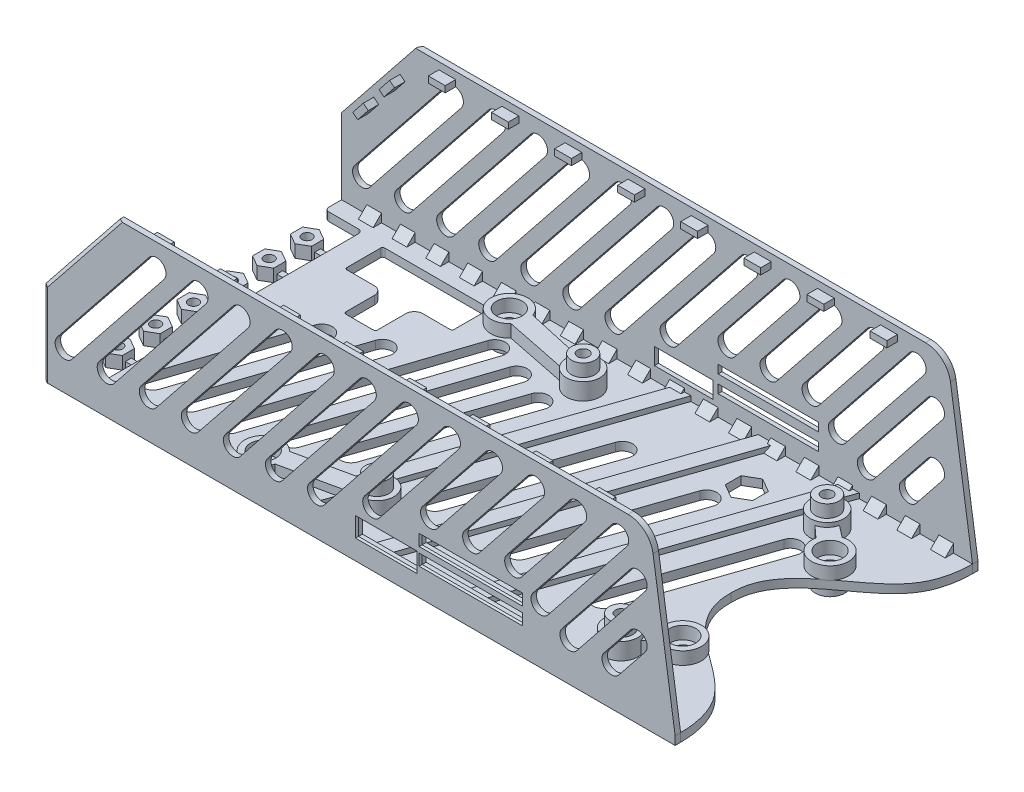
SolidWorks part; units mm, degrees
material "PPS"
ref_plane "前视基准面" through (0, 0, 0) normal (0, 0, 1) x (1, 0, 0)
ref_plane "上视基准面" through (0, 0, 0) normal (0, 1, 0) x (1, 0, 0)
ref_plane "右视基准面" through (0, 0, 0) normal (1, 0, 0) x (0, 0, -1)
sketch "草图1" plane through (0, 0, 0) normal (0, 1, 0) x (1, 0, 0)
  line L1 (-38.5883, 74.1339) -> (111.4117, 74.1339)
  line L2 (-38.5883, 74.1339) -> (-38.5883, 2.1339)
  line L3 (-38.5883, 2.1339) -> (111.4117, 2.1339)
  line L4 (111.4117, 74.1339) -> (111.4117, 2.1339)
  dimension "D1" = 72
  dimension "D2" = 150
extrude "底板" add sketch "草图1" against normal blind 2 contours L2 L1 L4 L3
sketch "草图2" plane through (0, 0, 0) normal (0, 1, 0) x (1, 0, 0)
  circle A3 centre (28.7548, 13.929) radius 4
  circle A4 centre (86.7548, 13.929) radius 4
  circle A5 centre (86.7548, 62.929) radius 4
  circle A6 centre (28.7548, 62.929) radius 4
  dimension "D1" = 2
  dimension "D2" = 2
extrude "板卡固定柱" add sketch "草图2" along normal blind 7
sketch "螺母孔" plane through (0, -2, 0) normal (0, -1, 0) x (1, 0, 0)
  line L0 (88.256, -11.329) -> (85.2537, -11.329)
  line L1 (30.256, -11.329) -> (27.2537, -11.329)
  line L2 (27.2537, -11.329) -> (25.7526, -13.929)
  line L3 (25.7526, -13.929) -> (27.2537, -16.529)
  line L4 (27.2537, -16.529) -> (30.256, -16.529)
  line L5 (30.256, -16.529) -> (31.7571, -13.929)
  line L6 (31.7571, -13.929) -> (30.256, -11.329)
  line L7 (85.2537, -11.329) -> (83.7526, -13.929)
  line L8 (83.7526, -13.929) -> (85.2537, -16.529)
  line L9 (85.2537, -16.529) -> (88.256, -16.529)
  line L10 (88.256, -16.529) -> (89.7571, -13.929)
  line L11 (89.7571, -13.929) -> (88.256, -11.329)
  line L12 (88.256, -60.329) -> (85.2537, -60.329)
  line L13 (85.2537, -60.329) -> (83.7526, -62.929)
  line L14 (83.7526, -62.929) -> (85.2537, -65.529)
  line L15 (85.2537, -65.529) -> (88.256, -65.529)
  line L16 (88.256, -65.529) -> (89.7571, -62.929)
  line L17 (89.7571, -62.929) -> (88.256, -60.329)
  line L18 (30.256, -60.329) -> (27.2537, -60.329)
  line L19 (27.2537, -60.329) -> (25.7526, -62.929)
  line L20 (25.7526, -62.929) -> (27.2537, -65.529)
  line L21 (27.2537, -65.529) -> (30.256, -65.529)
  line L22 (30.256, -65.529) -> (31.7571, -62.929)
  line L23 (31.7571, -62.929) -> (30.256, -60.329)
  circle A0 centre (28.7548, -13.929) radius 2.6 construction
  circle A1 centre (28.7548, -13.929) radius 4 construction
  circle A2 centre (86.7548, -13.929) radius 2.6 construction
  circle A3 centre (86.7548, -62.929) radius 2.6 construction
  circle A4 centre (28.7548, -62.929) radius 2.6 construction
  dimension "D1" = 2
  dimension "D2" = 2
extrude "m2.5螺母孔槽" cut sketch "螺母孔" against normal blind 5
sketch "草图4" plane through (0, 3, 0) normal (0, -1, 0) x (1, 0, 0)
  circle A0 centre (28.7548, -13.929) radius 1.35
  circle A1 centre (28.7548, -13.929) radius 4 construction
  circle A2 centre (86.7548, -13.929) radius 1.35
  circle A3 centre (86.7548, -62.929) radius 1.35
  circle A4 centre (28.7548, -62.929) radius 1.35
  dimension "D1" = 2
  dimension "D2" = 2
extrude "m2.5通孔" cut sketch "草图4" against normal up to next
sketch "草图6" plane through (0, 7, 0) normal (0, 1, 0) x (1, 0, 0)
  circle A0 centre (28.7548, 13.929) radius 4
  circle A1 centre (28.7548, 13.929) radius 2.7944
  circle A2 centre (86.7548, 13.929) radius 4
  circle A3 centre (86.7548, 13.929) radius 2.7944
  circle A4 centre (86.7548, 62.929) radius 4
  circle A5 centre (86.7548, 62.929) radius 2.7944
  circle A6 centre (28.7548, 62.929) radius 4
  circle A7 centre (28.7548, 62.929) radius 2.7944
  dimension "D1" = 2
  dimension "D2" = 2
extrude "切除-拉伸3" cut sketch "草图6" against normal blind 3
sketch "侧边" plane through (0, 0, -74.1339) normal (0, 0, -1) x (-1, 0, 0)
  line L0 (-74.7943, 6.8381) -> (-50.9153, 6.8381)
  line L1 (-111.4117, 0) -> (38.5883, 0)
  line L6 (-74.7943, 10.8959) -> (-50.9153, 10.8959)
  line L8 (-74.7943, 10.8959) -> (-74.7943, 8.8959)
  line L9 (-74.7943, 4.8381) -> (-50.9153, 4.8381)
  line L10 (-50.9153, 4.8381) -> (-50.9153, 6.8381)
  line L11 (-74.7943, 8.8959) -> (-50.9153, 8.8959)
  line L12 (-74.7943, 6.8381) -> (-74.7943, 4.8381)
  line L13 (-50.9153, 8.8959) -> (-50.9153, 10.8959)
  line L16 (-49.6686, 3.0554) -> (-35.7948, 3.0554)
  line L17 (-35.7948, 3.0554) -> (-35.7948, 7)
  line L18 (-35.7948, 7) -> (-49.6686, 7)
  line L19 (-49.6686, 7) -> (-49.6686, 3.0554)
  line L21 (38.5883, -2) -> (38.5883, 0) construction
  line L22 (20.9589, 40) -> (-100.2254, 40)
  line L23 (-106.1585, 34.8932) -> (-111.4117, 0)
  line L25 (38.5883, 0) -> (38.5883, 17.9447)
  line L26 (38.5883, 17.9447) -> (20.9589, 40)
  line L27 (33.7328, 7.228) -> (11.8797, 34.5674) construction
  line L28 (31.9753, 5.8231) -> (10.1222, 33.1625)
  line L29 (35.4903, 8.6328) -> (13.6373, 35.9722)
  line L30 (23.7328, 7.228) -> (1.8797, 34.5674) construction
  line L31 (21.9753, 5.8231) -> (0.1222, 33.1625)
  line L32 (25.4903, 8.6328) -> (3.6373, 35.9722)
  line L33 (13.7328, 7.228) -> (-8.1203, 34.5674) construction
  line L34 (11.9753, 5.8231) -> (-9.8778, 33.1625)
  line L35 (15.4903, 8.6328) -> (-6.3627, 35.9722)
  line L36 (3.7328, 7.228) -> (-18.1203, 34.5674) construction
  line L37 (1.9753, 5.8231) -> (-19.8778, 33.1625)
  line L38 (5.4903, 8.6328) -> (-16.3627, 35.9722)
  line L39 (-6.2672, 7.228) -> (-28.1203, 34.5674) construction
  line L40 (-8.0247, 5.8231) -> (-29.8778, 33.1625)
  line L41 (-4.5097, 8.6328) -> (-26.3627, 35.9722)
  line L42 (-16.2672, 7.228) -> (-38.1203, 34.5674) construction
  line L43 (-18.0247, 5.8231) -> (-39.8778, 33.1625)
  line L44 (-14.5097, 8.6328) -> (-36.3627, 35.9722)
  line L45 (-26.2672, 7.228) -> (-48.1203, 34.5674) construction
  line L46 (-28.0247, 5.8231) -> (-49.8778, 33.1625)
  line L47 (-24.5097, 8.6328) -> (-46.3627, 35.9722)
  line L48 (-39.3891, 11.1336) -> (-58.1203, 34.5674) construction
  line L49 (-41.1466, 9.7287) -> (-59.8778, 33.1625)
  line L50 (-37.6315, 12.5384) -> (-56.3627, 35.9722)
  line L51 (-53.1353, 15.8203) -> (-68.1203, 34.5674) construction
  line L52 (-54.8928, 14.4155) -> (-69.8778, 33.1625)
  line L53 (-51.3778, 17.2252) -> (-66.3627, 35.9722)
  line L54 (-63.1353, 15.8203) -> (-78.1203, 34.5674) construction
  line L55 (-64.8928, 14.4155) -> (-79.8778, 33.1625)
  line L56 (-61.3778, 17.2252) -> (-76.3627, 35.9722)
  line L57 (-73.1353, 15.8203) -> (-88.1203, 34.5674) construction
  line L58 (-74.8928, 14.4155) -> (-89.8778, 33.1625)
  line L59 (-71.3778, 17.2252) -> (-86.3627, 35.9722)
  line L60 (-79.3891, 11.1336) -> (-98.1203, 34.5674) construction
  line L61 (-81.1466, 9.7287) -> (-99.8778, 33.1625)
  line L62 (-77.6315, 12.5384) -> (-96.3627, 35.9722)
  line L63 (-86.2672, 7.228) -> (-102.5009, 27.5372) construction
  line L64 (-88.0247, 5.8231) -> (-104.2584, 26.1324)
  line L65 (-84.5097, 8.6328) -> (-100.7434, 28.9421)
  line L66 (-96.2672, 7.228) -> (-102.5109, 15.0392) construction
  line L67 (-98.0247, 5.8231) -> (-104.2685, 13.6344)
  line L68 (-94.5097, 8.6328) -> (-100.7534, 16.4441)
  arc A0 (-100.2254, 40) -> (-106.1585, 34.8932) centre (-100.2254, 34) ccw
  arc A1 (31.9753, 5.8231) -> (35.4903, 8.6328) centre (33.7328, 7.228) ccw
  arc A2 (13.6373, 35.9722) -> (10.1222, 33.1625) centre (11.8797, 34.5674) ccw
  arc A3 (21.9753, 5.8231) -> (25.4903, 8.6328) centre (23.7328, 7.228) ccw
  arc A4 (3.6373, 35.9722) -> (0.1222, 33.1625) centre (1.8797, 34.5674) ccw
  arc A5 (11.9753, 5.8231) -> (15.4903, 8.6328) centre (13.7328, 7.228) ccw
  arc A6 (-6.3627, 35.9722) -> (-9.8778, 33.1625) centre (-8.1203, 34.5674) ccw
  arc A7 (1.9753, 5.8231) -> (5.4903, 8.6328) centre (3.7328, 7.228) ccw
  arc A8 (-16.3627, 35.9722) -> (-19.8778, 33.1625) centre (-18.1203, 34.5674) ccw
  arc A9 (-8.0247, 5.8231) -> (-4.5097, 8.6328) centre (-6.2672, 7.228) ccw
  arc A10 (-26.3627, 35.9722) -> (-29.8778, 33.1625) centre (-28.1203, 34.5674) ccw
  arc A11 (-18.0247, 5.8231) -> (-14.5097, 8.6328) centre (-16.2672, 7.228) ccw
  arc A12 (-36.3627, 35.9722) -> (-39.8778, 33.1625) centre (-38.1203, 34.5674) ccw
  arc A13 (-28.0247, 5.8231) -> (-24.5097, 8.6328) centre (-26.2672, 7.228) ccw
  arc A14 (-46.3627, 35.9722) -> (-49.8778, 33.1625) centre (-48.1203, 34.5674) ccw
  arc A15 (-41.1466, 9.7287) -> (-37.6315, 12.5384) centre (-39.3891, 11.1336) ccw
  arc A16 (-56.3627, 35.9722) -> (-59.8778, 33.1625) centre (-58.1203, 34.5674) ccw
  arc A17 (-54.8928, 14.4155) -> (-51.3778, 17.2252) centre (-53.1353, 15.8203) ccw
  arc A18 (-66.3627, 35.9722) -> (-69.8778, 33.1625) centre (-68.1203, 34.5674) ccw
  arc A19 (-64.8928, 14.4155) -> (-61.3778, 17.2252) centre (-63.1353, 15.8203) ccw
  arc A20 (-76.3627, 35.9722) -> (-79.8778, 33.1625) centre (-78.1203, 34.5674) ccw
  arc A21 (-74.8928, 14.4155) -> (-71.3778, 17.2252) centre (-73.1353, 15.8203) ccw
  arc A22 (-86.3627, 35.9722) -> (-89.8778, 33.1625) centre (-88.1203, 34.5674) ccw
  arc A23 (-81.1466, 9.7287) -> (-77.6315, 12.5384) centre (-79.3891, 11.1336) ccw
  arc A24 (-96.3627, 35.9722) -> (-99.8778, 33.1625) centre (-98.1203, 34.5674) ccw
  arc A25 (-88.0247, 5.8231) -> (-84.5097, 8.6328) centre (-86.2672, 7.228) ccw
  arc A26 (-100.7434, 28.9421) -> (-104.2584, 26.1324) centre (-102.5009, 27.5372) ccw
  arc A27 (-98.0247, 5.8231) -> (-94.5097, 8.6328) centre (-96.2672, 7.228) ccw
  arc A28 (-100.7534, 16.4441) -> (-104.2685, 13.6344) centre (-102.5109, 15.0392) ccw
  point P2 (22.8063, 20.8977)
  point P26 (0, 0)
  point P27 (0, 0)
  point P30 (0, 0)
  point P31 (12.8063, 20.8977)
  point P38 (2.8063, 20.8977)
  point P40 (0, 0)
  point P48 (-7.1937, 20.8977)
  point P55 (-17.1937, 20.8977)
  point P62 (-27.1937, 20.8977)
  point P69 (-37.1937, 20.8977)
  point P76 (-48.7547, 22.8505)
  point P83 (-60.6278, 25.1939)
  point P90 (-70.6278, 25.1939)
  point P97 (-80.6278, 25.1939)
  point P104 (-88.7547, 22.8505)
  point P111 (-94.384, 17.3826)
  point P118 (-99.3891, 11.1336)
  point P125 (0, 0)
  point P126 (0, 0)
  point P127 (0, 0)
  point P128 (0, 0)
  point P129 (0, 0)
  point P130 (0, 0)
  point P131 (0, 0)
  point P132 (0, 0)
  point P133 (0, 0)
  point P134 (0, 0)
  point P135 (0, 0)
  point P136 (0, 0)
  point P137 (0, 0)
  point P138 (0, 0)
  dimension "D1" = 6
  dimension "D2" = 40
extrude "侧边凸台" add sketch "侧边" against normal blind 1.3
sketch "草图14" plane through (0, 0, -72.8339) normal (0, 0, 1) x (1, 0, 0)
  line L0 (-30.9262, 24.9677) -> (-33.4237, 21.8432)
  line L1 (-33.4237, 21.8432) -> (-32.2521, 20.9067)
  line L2 (-24.6825, 32.779) -> (-27.18, 29.6545)
  line L3 (-27.18, 29.6545) -> (-26.0083, 28.7179)
  line L4 (-26.0083, 28.7179) -> (-23.5108, 31.8424)
  line L5 (-23.5108, 31.8424) -> (-24.6825, 32.779)
  line L6 (-32.2521, 20.9067) -> (-29.7546, 24.0312)
  line L7 (-29.7546, 24.0312) -> (-30.9262, 24.9677)
  line L9 (-15.4544, 38.32) -> (-11.4544, 38.32)
  line L10 (-11.4544, 38.32) -> (-11.4544, 36.82)
  line L11 (-11.4544, 36.82) -> (-15.4544, 36.82)
  line L12 (-15.4544, 36.82) -> (-15.4544, 38.32)
  line L13 (-20.9589, 40) -> (100.2254, 40) construction
  line L14 (-0.4544, 38.32) -> (3.5456, 38.32)
  line L15 (3.5456, 38.32) -> (3.5456, 36.82)
  line L16 (3.5456, 36.82) -> (-0.4544, 36.82)
  line L17 (-0.4544, 36.82) -> (-0.4544, 38.32)
  line L18 (14.5456, 38.32) -> (18.5456, 38.32)
  line L19 (18.5456, 38.32) -> (18.5456, 36.82)
  line L20 (18.5456, 36.82) -> (14.5456, 36.82)
  line L21 (14.5456, 36.82) -> (14.5456, 38.32)
  line L22 (29.5456, 38.32) -> (33.5456, 38.32)
  line L23 (33.5456, 38.32) -> (33.5456, 36.82)
  line L24 (33.5456, 36.82) -> (29.5456, 36.82)
  line L25 (29.5456, 36.82) -> (29.5456, 38.32)
  line L26 (44.5456, 38.32) -> (48.5456, 38.32)
  line L27 (48.5456, 38.32) -> (48.5456, 36.82)
  line L28 (48.5456, 36.82) -> (44.5456, 36.82)
  line L29 (44.5456, 36.82) -> (44.5456, 38.32)
  line L30 (59.5456, 38.32) -> (63.5456, 38.32)
  line L31 (63.5456, 38.32) -> (63.5456, 36.82)
  line L32 (63.5456, 36.82) -> (59.5456, 36.82)
  line L33 (59.5456, 36.82) -> (59.5456, 38.32)
  line L34 (74.5456, 38.32) -> (78.5456, 38.32)
  line L35 (78.5456, 38.32) -> (78.5456, 36.82)
  line L36 (78.5456, 36.82) -> (74.5456, 36.82)
  line L37 (74.5456, 36.82) -> (74.5456, 38.32)
  line L38 (89.5456, 38.32) -> (93.5456, 38.32)
  line L39 (93.5456, 38.32) -> (93.5456, 36.82)
  line L40 (93.5456, 36.82) -> (89.5456, 36.82)
  line L41 (89.5456, 36.82) -> (89.5456, 38.32)
  dimension "D1" = 2
  dimension "D2" = 1.68
  dimension "D3" = 1.5
  dimension "D4" = 4
  dimension "D5" = 8
extrude "顶盖支架" add sketch "草图14" along normal blind 2.5
sketch "草图15" plane through (0, -2, 0) normal (0, -1, 0) x (1, 0, 0)
  line L0 (-38.5883, -38.1339) -> (111.4117, -38.1339)
  line L1 (-38.5883, -74.1339) -> (-38.5883, -2.1339) construction
  line L2 (111.4117, -74.1339) -> (111.4117, -2.1339) construction
ref_plane "基准面7" through (0, 0, -38.1339) normal (0, 0, -1) x (-1, 0, 0)
mirror "镜向1" about plane through (0, 0, -38.1339) normal (0, 0, -1) of "侧边凸台", "顶盖支架"
sketch "草图17" plane through (0, -2, 0) normal (0, -1, 0) x (1, 0, 0)
  line L0 (-7.5175, -59.0417) -> (1.4825, -59.0417)
  line L1 (1.4825, -59.0417) -> (1.4825, -68.0417)
  line L6 (1.4825, -68.0417) -> (-24.0175, -68.0417)
  line L7 (-24.0175, -68.0417) -> (-24.0175, -59.0417)
  line L8 (-24.0175, -59.0417) -> (-15.0175, -59.0417)
  line L9 (6.7325, -8.8917) -> (6.7325, -67.3917)
  line L10 (6.7325, -67.3917) -> (6.7325, -38.1417)
  line L11 (-7.5175, -49.7917) -> (-15.0175, -49.7917)
  line L12 (-7.5175, -59.0417) -> (-7.5175, -49.7917)
  line L14 (-15.0175, -49.7917) -> (-15.0175, -59.0417)
  line L15 (6.7325, -38.1417) -> (17.9206, -38.1417)
  circle A6 centre (6.7325, -67.3917) radius 1.55
  circle A7 centre (94.7325, -55.6417) radius 1.55
  circle A8 centre (6.7325, -67.3917) radius 1.55
  circle A9 centre (94.7325, -20.6417) radius 1.55
  circle A10 centre (6.7325, -8.8917) radius 1.55
  dimension "D1" = 9
  dimension "D2" = 9
  dimension "D3" = 9
  dimension "D4" = 58.5
extrude "链接孔" cut sketch "草图17" against normal blind 7 and the other way blind 13 contours A6 | L11 L14 L12 | A7 | A9 | A10 region at (-11.2675, -2, -61.4236) region at (7.7975, -2, -66.3267)
sketch "草图27" plane through (0, -2, 0) normal (0, -1, 0) x (1, 0, 0)
  circle A0 centre (94.7325, -55.6417) radius 3.5
  circle A1 centre (94.7325, -20.6417) radius 3.5
  circle A2 centre (6.7325, -67.3917) radius 3.5
  circle A3 centre (6.7325, -8.8917) radius 3.5
  dimension "D1" = 7
extrude "凸台-拉伸9" add sketch "草图27" along normal blind 2
sketch "草图18" plane through (0, 0, 0) normal (0, 1, 0) x (1, 0, 0)
  line L0 (-38.5883, 7.4339) -> (-38.5883, 68.8339)
  line L13 (-23.5883, 13.0192) -> (-13.5883, 43.1339) construction
  line L14 (23.1, 38.1339) -> (-23.1, 38.1339) construction
  line L15 (-25.9609, 13.8071) -> (-15.9609, 43.9218)
  line L22 (-21.2157, 12.2314) -> (-11.2157, 42.3461)
  line L23 (-38.5883, 7.4339) -> (-30.5883, 7.4339)
  line L24 (-29.5883, 8.4339) -> (-29.5883, 67.8339)
  line L25 (-30.5883, 68.8339) -> (-38.5883, 68.8339)
  line L26 (-38.5883, 38.1339) -> (111.4117, 38.1339) construction
  line L27 (-14.5883, 13.0192) -> (-3.2431, 47.1848) construction
  line L28 (-16.9609, 13.8071) -> (-5.6157, 47.9727)
  line L29 (-12.2157, 12.2314) -> (-0.8705, 46.3969)
  line L30 (-5.5883, 13.0192) -> (10.1689, 60.4714) construction
  line L31 (-7.9609, 13.8071) -> (7.7963, 61.2593)
  line L32 (-3.2157, 12.2314) -> (12.5415, 59.6836)
  line L33 (4.9874, 17.7644) -> (18.2234, 57.6243) construction
  line L34 (2.6148, 18.5523) -> (15.8508, 58.4121)
  line L35 (7.36, 16.9766) -> (20.596, 56.8364)
  line L36 (14.9242, 21.5786) -> (26.2679, 54.6893) construction
  line L37 (12.5591, 22.3889) -> (23.9029, 55.4996)
  line L38 (17.2892, 20.7683) -> (28.633, 53.879)
  line L39 (111.4117, 72.8339) -> (-38.5883, 72.8339) construction
  line L41 (111.4117, 72.8339) -> (111.4117, 3.4339)
  line L44 (34.9242, 21.5786) -> (46.2679, 54.6893) construction
  line L45 (32.5591, 22.3889) -> (43.9029, 55.4996)
  line L46 (37.2892, 20.7683) -> (48.633, 53.879)
  line L50 (54.9242, 21.5786) -> (66.2679, 54.6893) construction
  line L51 (52.5591, 22.3889) -> (63.9029, 55.4996)
  line L52 (57.2892, 20.7683) -> (68.633, 53.879)
  line L56 (74.9242, 21.5786) -> (86.2679, 54.6893) construction
  line L57 (72.5591, 22.3889) -> (83.9029, 55.4996)
  line L58 (77.2892, 20.7683) -> (88.633, 53.879)
  line L264 (44.9242, 21.5786) -> (56.2679, 54.6893) construction
  line L265 (42.5591, 22.3889) -> (53.9029, 55.4996)
  line L266 (47.2892, 20.7683) -> (58.633, 53.879)
  line L267 (64.9242, 21.5786) -> (76.2679, 54.6893) construction
  line L268 (62.5591, 22.3889) -> (73.9029, 55.4996)
  line L269 (67.2892, 20.7683) -> (78.633, 53.879)
  line L270 (24.9242, 21.5786) -> (36.2679, 54.6893) construction
  line L271 (22.5591, 22.3889) -> (33.9029, 55.4996)
  line L272 (27.2892, 20.7683) -> (38.633, 53.879)
  line L273 (44.9242, 21.5786) -> (56.2679, 54.6893) construction
  line L274 (42.5591, 22.3889) -> (53.9029, 55.4996)
  line L275 (47.2892, 20.7683) -> (58.633, 53.879)
  line L276 (64.9242, 21.5786) -> (76.2679, 54.6893) construction
  line L277 (62.5591, 22.3889) -> (73.9029, 55.4996)
  line L278 (67.2892, 20.7683) -> (78.633, 53.879)
  line L279 (24.9242, 21.5786) -> (36.2679, 54.6893) construction
  line L280 (22.5591, 22.3889) -> (33.9029, 55.4996)
  line L281 (27.2892, 20.7683) -> (38.633, 53.879)
  arc A2 (-25.9609, 13.8071) -> (-21.2157, 12.2314) centre (-23.5883, 13.0192) ccw
  arc A3 (-11.2157, 42.3461) -> (-15.9609, 43.9218) centre (-13.5883, 43.1339) ccw
  arc A4 (-16.9609, 13.8071) -> (-12.2157, 12.2314) centre (-14.5883, 13.0192) ccw
  arc A5 (-0.8705, 46.3969) -> (-5.6157, 47.9727) centre (-3.2431, 47.1848) ccw
  arc A6 (-7.9609, 13.8071) -> (-3.2157, 12.2314) centre (-5.5883, 13.0192) ccw
  arc A7 (12.5415, 59.6836) -> (7.7963, 61.2593) centre (10.1689, 60.4714) ccw
  arc A8 (2.6148, 18.5523) -> (7.36, 16.9766) centre (4.9874, 17.7644) ccw
  arc A9 (20.596, 56.8364) -> (15.8508, 58.4121) centre (18.2234, 57.6243) ccw
  arc A10 (12.5591, 22.3889) -> (17.2892, 20.7683) centre (14.9242, 21.5786) ccw
  arc A11 (28.633, 53.879) -> (23.9029, 55.4996) centre (26.2679, 54.6893) ccw
  arc A18 (-30.5883, 7.4339) -> (-29.5883, 8.4339) centre (-30.5883, 8.4339) ccw
  arc A19 (-29.5883, 67.8339) -> (-30.5883, 68.8339) centre (-30.5883, 67.8339) ccw
  arc A21 (32.5591, 22.3889) -> (37.2892, 20.7683) centre (34.9242, 21.5786) ccw
  arc A22 (48.633, 53.879) -> (43.9029, 55.4996) centre (46.2679, 54.6893) ccw
  arc A25 (52.5591, 22.3889) -> (57.2892, 20.7683) centre (54.9242, 21.5786) ccw
  arc A26 (68.633, 53.879) -> (63.9029, 55.4996) centre (66.2679, 54.6893) ccw
  arc A29 (72.5591, 22.3889) -> (77.2892, 20.7683) centre (74.9242, 21.5786) ccw
  arc A30 (88.633, 53.879) -> (83.9029, 55.4996) centre (86.2679, 54.6893) ccw
  arc A174 (42.5591, 22.3889) -> (47.2892, 20.7683) centre (44.9242, 21.5786) ccw
  arc A175 (58.633, 53.879) -> (53.9029, 55.4996) centre (56.2679, 54.6893) ccw
  arc A176 (62.5591, 22.3889) -> (67.2892, 20.7683) centre (64.9242, 21.5786) ccw
  arc A177 (78.633, 53.879) -> (73.9029, 55.4996) centre (76.2679, 54.6893) ccw
  arc A178 (22.5591, 22.3889) -> (27.2892, 20.7683) centre (24.9242, 21.5786) ccw
  arc A179 (38.633, 53.879) -> (33.9029, 55.4996) centre (36.2679, 54.6893) ccw
  spline S0 degree 3 poles (111.4117, 72.8339) (111.3592, 67.7048) (109.4998, 62.8559) (100.5415, 53.3454) (88.3796, 48.3908) (88.633, 38.1339) knots 0 0 0 0 0.239028 0.339028 1 1 1 1
  spline S1 degree 3 poles (111.4117, 3.4339) (111.3592, 8.5631) (109.4998, 13.412) (100.5415, 22.9225) (88.3796, 27.8771) (88.633, 38.1339) knots 0 0 0 0 0.239028 0.339028 1 1 1 1
  point P6 (50.596, 38.1339)
  point P20 (-18.5883, 28.0766)
  point P31 (-8.9157, 30.102)
  point P38 (2.2903, 36.7453)
  point P44 (40.596, 38.1339)
  point P47 (11.6054, 37.6944)
  point P54 (20.596, 38.1339)
  point P65 (30.596, 38.1339)
  point P68 (28.7548, 38.1339)
  point P72 (70.596, 38.1339)
  point P82 (-29.5883, 7.4339)
  point P87 (60.596, 38.1339)
  point P101 (80.596, 38.1339)
  point P109 (50.596, 38.1339)
  point P116 (70.596, 38.1339)
  point P123 (30.596, 38.1339)
  point P130 (50.596, 38.1339)
  point P137 (70.596, 38.1339)
  point P144 (30.596, 38.1339)
  point P151 (50.596, 38.1339)
  point P158 (70.596, 38.1339)
  point P165 (30.596, 38.1339)
  point P172 (50.596, 38.1339)
  point P179 (70.596, 38.1339)
  point P186 (30.596, 38.1339)
  point P193 (50.596, 38.1339)
  point P200 (70.596, 38.1339)
  point P207 (30.596, 38.1339)
  point P214 (50.596, 38.1339)
  point P221 (70.596, 38.1339)
  point P228 (30.596, 38.1339)
  point P235 (50.596, 38.1339)
  point P242 (70.596, 38.1339)
  point P249 (30.596, 38.1339)
  point P256 (50.596, 38.1339)
  point P263 (70.596, 38.1339)
  point P270 (30.596, 38.1339)
  point P277 (50.596, 38.1339)
  point P284 (70.596, 38.1339)
  point P291 (30.596, 38.1339)
  point P298 (50.596, 38.1339)
  point P305 (70.596, 38.1339)
  point P312 (30.596, 38.1339)
  point P319 (50.596, 38.1339)
  point P326 (70.596, 38.1339)
  point P333 (30.596, 38.1339)
  point P340 (50.596, 38.1339)
  point P347 (70.596, 38.1339)
  point P354 (30.596, 38.1339)
  point P361 (50.596, 38.1339)
  point P368 (70.596, 38.1339)
  point P375 (30.596, 38.1339)
  point P382 (50.596, 38.1339)
  point P389 (70.596, 38.1339)
  point P396 (30.596, 38.1339)
  point P403 (50.596, 38.1339)
  point P410 (70.596, 38.1339)
  point P417 (30.596, 38.1339)
  point P424 (50.596, 38.1339)
  point P431 (70.596, 38.1339)
  point P438 (30.596, 38.1339)
  point P445 (50.596, 38.1339)
  point P452 (70.596, 38.1339)
  point P459 (30.596, 38.1339)
  point P466 (50.596, 38.1339)
  point P473 (70.596, 38.1339)
  point P480 (30.596, 38.1339)
  point P487 (50.596, 38.1339)
  point P494 (70.596, 38.1339)
  point P501 (30.596, 38.1339)
  point P508 (50.596, 38.1339)
  point P515 (70.596, 38.1339)
  point P522 (30.596, 38.1339)
  point P529 (50.596, 38.1339)
  point P536 (70.596, 38.1339)
  point P543 (30.596, 38.1339)
  point P550 (50.596, 38.1339)
  point P557 (70.596, 38.1339)
  point P564 (30.596, 38.1339)
  point P571 (50.596, 38.1339)
  point P578 (70.596, 38.1339)
  point P585 (30.596, 38.1339)
  point P592 (50.596, 38.1339)
  point P599 (70.596, 38.1339)
  point P606 (30.596, 38.1339)
  dimension "D8" = 2.5
  dimension "D1" = 0
  dimension "D2" = 7
  dimension "D6" = 9
  dimension "D7" = 6
  dimension "D9" = 5
  dimension "D10" = 16
  dimension "D11" = 12.3625
extrude "切除-拉伸6" cut sketch "草图18" against normal up to next
fillet "圆角3" radius 1 2 edges at (-38.5883, -1, -7.4339) (-38.5883, -1, -68.8339)
sketch "草图21" plane through (0, 0, 0) normal (0, 1, 0) x (1, 0, 0)
  line L19 (25.2623, 61.392) -> (10.0302, 64.4787)
  line L21 (25.8951, 65.4552) -> (10.904, 68.7911)
  line L24 (25.2432, 15.1377) -> (9.9931, 11.8461)
  line L26 (26.1715, 10.8368) -> (10.9214, 7.5452)
  line L32 (90.4004, 19.8717) -> (87.7239, 17.6196)
  line L33 (93.2333, 16.505) -> (90.5117, 14.5967)
  line L36 (87.573, 59.202) -> (90.4353, 56.5873)
  line L38 (90.4814, 62.1089) -> (93.4028, 59.836)
  arc A12 (10.904, 68.7911) -> (10.0302, 64.4787) centre (6.7325, 67.3917) ccw
  circle A13 centre (6.7325, 67.3917) radius 3.05
  arc A14 (25.8951, 65.4552) -> (25.2623, 61.392) centre (28.7548, 62.929) ccw
  arc A15 (9.9931, 11.8461) -> (10.9214, 7.5452) centre (6.7325, 8.8917) ccw
  circle A16 centre (6.7325, 8.8917) radius 3.05
  arc A17 (25.2432, 15.1377) -> (26.1715, 10.8368) centre (28.9728, 13.692) ccw
  arc A18 (93.2333, 16.505) -> (90.4004, 19.8717) centre (94.7325, 20.6417) ccw
  circle A19 centre (94.7325, 20.6417) radius 3.05
  arc A20 (90.5117, 14.5967) -> (87.7239, 17.6196) centre (86.7548, 13.929) ccw
  arc A21 (90.4353, 56.5873) -> (93.4028, 59.836) centre (94.7325, 55.6417) ccw
  circle A22 centre (94.7325, 55.6417) radius 3.05
  arc A23 (87.573, 59.202) -> (90.4814, 62.1089) centre (86.7548, 62.929) ccw
  dimension "D1" = 6.1
  dimension "D2" = 4.4
extrude "板卡固定加强筋" add sketch "草图21" along normal blind 3
sketch "草图23" plane through (0, 0, 0) normal (0, 1, 0) x (1, 0, 0)
  line L0 (111.4117, 72.8339) -> (-38.5883, 72.8339) construction
  line L1 (-32.5883, 72.8339) -> (-29.0883, 72.8339)
  line L2 (-32.5883, 72.8339) -> (-32.5883, 70.8339)
  line L3 (-32.5883, 70.8339) -> (-29.0883, 70.8339)
  line L4 (-29.0883, 72.8339) -> (-29.0883, 70.8339)
  line L5 (-24.5883, 72.8339) -> (-24.5883, 70.8339)
  line L6 (-24.5883, 72.8339) -> (-21.0883, 72.8339)
  line L7 (-24.5883, 70.8339) -> (-21.0883, 70.8339)
  line L8 (-21.0883, 72.8339) -> (-21.0883, 70.8339)
  line L9 (-16.5883, 72.8339) -> (-16.5883, 70.8339)
  line L10 (-16.5883, 72.8339) -> (-13.0883, 72.8339)
  line L11 (-16.5883, 70.8339) -> (-13.0883, 70.8339)
  line L12 (-13.0883, 72.8339) -> (-13.0883, 70.8339)
  line L13 (-8.5883, 72.8339) -> (-8.5883, 70.8339)
  line L14 (-8.5883, 72.8339) -> (-5.0883, 72.8339)
  line L15 (-8.5883, 70.8339) -> (-5.0883, 70.8339)
  line L16 (-5.0883, 72.8339) -> (-5.0883, 70.8339)
  line L17 (-0.5883, 72.8339) -> (-0.5883, 70.8339)
  line L18 (-0.5883, 72.8339) -> (2.9117, 72.8339)
  line L19 (-0.5883, 70.8339) -> (2.9117, 70.8339)
  line L20 (2.9117, 72.8339) -> (2.9117, 70.8339)
  line L21 (7.4117, 72.8339) -> (7.4117, 70.8339)
  line L22 (7.4117, 72.8339) -> (10.9117, 72.8339)
  line L23 (7.4117, 70.8339) -> (10.9117, 70.8339)
  line L24 (10.9117, 72.8339) -> (10.9117, 70.8339)
  line L25 (15.4117, 72.8339) -> (15.4117, 70.8339)
  line L26 (15.4117, 72.8339) -> (18.9117, 72.8339)
  line L27 (15.4117, 70.8339) -> (18.9117, 70.8339)
  line L28 (18.9117, 72.8339) -> (18.9117, 70.8339)
  line L29 (23.4117, 72.8339) -> (23.4117, 70.8339)
  line L30 (23.4117, 72.8339) -> (26.9117, 72.8339)
  line L31 (23.4117, 70.8339) -> (26.9117, 70.8339)
  line L32 (26.9117, 72.8339) -> (26.9117, 70.8339)
  line L33 (31.4117, 72.8339) -> (31.4117, 70.8339)
  line L34 (31.4117, 72.8339) -> (34.9117, 72.8339)
  line L35 (31.4117, 70.8339) -> (34.9117, 70.8339)
  line L36 (34.9117, 72.8339) -> (34.9117, 70.8339)
  line L37 (39.4117, 72.8339) -> (39.4117, 70.8339)
  line L38 (39.4117, 72.8339) -> (42.9117, 72.8339)
  line L39 (39.4117, 70.8339) -> (42.9117, 70.8339)
  line L40 (42.9117, 72.8339) -> (42.9117, 70.8339)
  line L41 (47.4117, 72.8339) -> (47.4117, 70.8339)
  line L42 (47.4117, 72.8339) -> (50.9117, 72.8339)
  line L43 (47.4117, 70.8339) -> (50.9117, 70.8339)
  line L44 (50.9117, 72.8339) -> (50.9117, 70.8339)
  line L45 (55.4117, 72.8339) -> (55.4117, 70.8339)
  line L46 (55.4117, 72.8339) -> (58.9117, 72.8339)
  line L47 (55.4117, 70.8339) -> (58.9117, 70.8339)
  line L48 (58.9117, 72.8339) -> (58.9117, 70.8339)
  line L49 (63.4117, 72.8339) -> (63.4117, 70.8339)
  line L50 (63.4117, 72.8339) -> (66.9117, 72.8339)
  line L51 (63.4117, 70.8339) -> (66.9117, 70.8339)
  line L52 (66.9117, 72.8339) -> (66.9117, 70.8339)
  line L53 (71.4117, 72.8339) -> (71.4117, 70.8339)
  line L54 (71.4117, 72.8339) -> (74.9117, 72.8339)
  line L55 (71.4117, 70.8339) -> (74.9117, 70.8339)
  line L56 (74.9117, 72.8339) -> (74.9117, 70.8339)
  line L57 (79.4117, 72.8339) -> (79.4117, 70.8339)
  line L58 (79.4117, 72.8339) -> (82.9117, 72.8339)
  line L59 (79.4117, 70.8339) -> (82.9117, 70.8339)
  line L60 (82.9117, 72.8339) -> (82.9117, 70.8339)
  line L61 (87.4117, 72.8339) -> (87.4117, 70.8339)
  line L62 (87.4117, 72.8339) -> (90.9117, 72.8339)
  line L63 (87.4117, 70.8339) -> (90.9117, 70.8339)
  line L64 (90.9117, 72.8339) -> (90.9117, 70.8339)
  line L65 (95.4117, 72.8339) -> (95.4117, 70.8339)
  line L66 (95.4117, 72.8339) -> (98.9117, 72.8339)
  line L67 (95.4117, 70.8339) -> (98.9117, 70.8339)
  line L68 (98.9117, 72.8339) -> (98.9117, 70.8339)
  line L69 (103.4117, 72.8339) -> (103.4117, 70.8339)
  line L70 (103.4117, 72.8339) -> (106.9117, 72.8339)
  line L71 (103.4117, 70.8339) -> (106.9117, 70.8339)
  line L72 (106.9117, 72.8339) -> (106.9117, 70.8339)
  line L73 (23.1, 38.1339) -> (-23.1, 38.1339) construction
  line L74 (106.9117, 3.4339) -> (106.9117, 5.4339)
  line L75 (103.4117, 5.4339) -> (106.9117, 5.4339)
  line L76 (103.4117, 3.4339) -> (106.9117, 3.4339)
  line L77 (103.4117, 3.4339) -> (103.4117, 5.4339)
  line L78 (98.9117, 3.4339) -> (98.9117, 5.4339)
  line L79 (95.4117, 5.4339) -> (98.9117, 5.4339)
  line L80 (95.4117, 3.4339) -> (98.9117, 3.4339)
  line L81 (95.4117, 3.4339) -> (95.4117, 5.4339)
  line L82 (90.9117, 3.4339) -> (90.9117, 5.4339)
  line L83 (87.4117, 5.4339) -> (90.9117, 5.4339)
  line L84 (87.4117, 3.4339) -> (90.9117, 3.4339)
  line L85 (87.4117, 3.4339) -> (87.4117, 5.4339)
  line L86 (82.9117, 3.4339) -> (82.9117, 5.4339)
  line L87 (79.4117, 5.4339) -> (82.9117, 5.4339)
  line L88 (79.4117, 3.4339) -> (82.9117, 3.4339)
  line L89 (79.4117, 3.4339) -> (79.4117, 5.4339)
  line L90 (74.9117, 3.4339) -> (74.9117, 5.4339)
  line L91 (71.4117, 5.4339) -> (74.9117, 5.4339)
  line L92 (71.4117, 3.4339) -> (74.9117, 3.4339)
  line L93 (71.4117, 3.4339) -> (71.4117, 5.4339)
  line L94 (66.9117, 3.4339) -> (66.9117, 5.4339)
  line L95 (63.4117, 5.4339) -> (66.9117, 5.4339)
  line L96 (63.4117, 3.4339) -> (66.9117, 3.4339)
  line L97 (63.4117, 3.4339) -> (63.4117, 5.4339)
  line L98 (58.9117, 3.4339) -> (58.9117, 5.4339)
  line L99 (55.4117, 5.4339) -> (58.9117, 5.4339)
  line L100 (55.4117, 3.4339) -> (58.9117, 3.4339)
  line L101 (55.4117, 3.4339) -> (55.4117, 5.4339)
  line L102 (50.9117, 3.4339) -> (50.9117, 5.4339)
  line L103 (47.4117, 5.4339) -> (50.9117, 5.4339)
  line L104 (47.4117, 3.4339) -> (50.9117, 3.4339)
  line L105 (47.4117, 3.4339) -> (47.4117, 5.4339)
  line L106 (42.9117, 3.4339) -> (42.9117, 5.4339)
  line L107 (39.4117, 5.4339) -> (42.9117, 5.4339)
  line L108 (39.4117, 3.4339) -> (42.9117, 3.4339)
  line L109 (39.4117, 3.4339) -> (39.4117, 5.4339)
  line L110 (34.9117, 3.4339) -> (34.9117, 5.4339)
  line L111 (31.4117, 5.4339) -> (34.9117, 5.4339)
  line L112 (31.4117, 3.4339) -> (34.9117, 3.4339)
  line L113 (31.4117, 3.4339) -> (31.4117, 5.4339)
  line L114 (26.9117, 3.4339) -> (26.9117, 5.4339)
  line L115 (23.4117, 5.4339) -> (26.9117, 5.4339)
  line L116 (23.4117, 3.4339) -> (26.9117, 3.4339)
  line L117 (23.4117, 3.4339) -> (23.4117, 5.4339)
  line L118 (18.9117, 3.4339) -> (18.9117, 5.4339)
  line L119 (15.4117, 5.4339) -> (18.9117, 5.4339)
  line L120 (15.4117, 3.4339) -> (18.9117, 3.4339)
  line L121 (15.4117, 3.4339) -> (15.4117, 5.4339)
  line L122 (10.9117, 3.4339) -> (10.9117, 5.4339)
  line L123 (7.4117, 5.4339) -> (10.9117, 5.4339)
  line L124 (7.4117, 3.4339) -> (10.9117, 3.4339)
  line L125 (7.4117, 3.4339) -> (7.4117, 5.4339)
  line L126 (2.9117, 3.4339) -> (2.9117, 5.4339)
  line L127 (-0.5883, 5.4339) -> (2.9117, 5.4339)
  line L128 (-0.5883, 3.4339) -> (2.9117, 3.4339)
  line L129 (-0.5883, 3.4339) -> (-0.5883, 5.4339)
  line L130 (-5.0883, 3.4339) -> (-5.0883, 5.4339)
  line L131 (-8.5883, 5.4339) -> (-5.0883, 5.4339)
  line L132 (-8.5883, 3.4339) -> (-5.0883, 3.4339)
  line L133 (-8.5883, 3.4339) -> (-8.5883, 5.4339)
  line L134 (-13.0883, 3.4339) -> (-13.0883, 5.4339)
  line L135 (-16.5883, 5.4339) -> (-13.0883, 5.4339)
  line L136 (-16.5883, 3.4339) -> (-13.0883, 3.4339)
  line L137 (-16.5883, 3.4339) -> (-16.5883, 5.4339)
  line L138 (-21.0883, 3.4339) -> (-21.0883, 5.4339)
  line L139 (-24.5883, 5.4339) -> (-21.0883, 5.4339)
  line L140 (-24.5883, 3.4339) -> (-21.0883, 3.4339)
  line L141 (-24.5883, 3.4339) -> (-24.5883, 5.4339)
  line L142 (-29.0883, 3.4339) -> (-29.0883, 5.4339)
  line L143 (-32.5883, 5.4339) -> (-29.0883, 5.4339)
  line L144 (-32.5883, 3.4339) -> (-32.5883, 5.4339)
  line L145 (-32.5883, 3.4339) -> (-29.0883, 3.4339)
  dimension "D1" = 6
  dimension "D2" = 3.5
  dimension "D3" = 2
  dimension "D4" = 18
extrude "凸台-拉伸7" add sketch "草图23" along normal blind 2.5
chamfer "倒角1" distance 2.5 angle 45 36 edges at (-30.8383, 2.5, -70.8339) (-22.8383, 2.5, -5.4339) (-30.8383, 2.5, -5.4339) (-14.8383, 2.5, -5.4339) (-6.8383, 2.5, -5.4339) (1.1617, 2.5, -5.4339) (10.1826, 2.5, -5.4339) (17.1617, 2.5, -5.4339) (25.1617, 2.5, -5.4339) (33.1617, 2.5, -5.4339) (41.1617, 2.5, -5.4339) (49.1617, 2.5, -5.4339) (57.1617, 2.5, -5.4339) (65.1617, 2.5, -5.4339) (73.1617, 2.5, -5.4339) (81.1617, 2.5, -5.4339) (89.1617, 2.5, -5.4339) (97.1617, 2.5, -5.4339) (105.1617, 2.5, -5.4339) (105.1617, 2.5, -70.8339) (97.1617, 2.5, -70.8339) (89.1617, 2.5, -70.8339) (81.1617, 2.5, -70.8339) (73.1617, 2.5, -70.8339) (65.1617, 2.5, -70.8339) (57.1617, 2.5, -70.8339) (49.1617, 2.5, -70.8339) (41.1617, 2.5, -70.8339) (33.1617, 2.5, -70.8339) (25.1617, 2.5, -70.8339) (17.1617, 2.5, -70.8339) (10.1924, 2.5, -70.8339) (1.1617, 2.5, -70.8339) (-6.8383, 2.5, -70.8339) (-14.8383, 2.5, -70.8339) (-22.8383, 2.5, -70.8339)
sketch "草图25" plane through (0, 0, 0) normal (0, 1, 0) x (1, 0, 0)
  line L8 (84.4843, 72.8339) -> (80.4843, 72.8339)
  line L10 (60.7078, 3.4339) -> (56.7078, 3.4339)
  line L11 (64.4843, 72.8339) -> (60.4843, 72.8339)
  line L12 (40.7078, 3.4339) -> (36.7078, 3.4339)
  line L13 (84.4843, 72.8339) -> (60.7078, 3.4339)
  line L14 (64.4843, 72.8339) -> (40.7078, 3.4339)
  line L15 (80.4843, 72.8339) -> (56.7078, 3.4339)
  line L16 (60.4843, 72.8339) -> (36.7078, 3.4339)
  line L17 (44.4843, 72.8339) -> (40.4843, 72.8339)
  line L18 (20.7078, 3.4339) -> (16.7078, 3.4339)
  line L19 (44.4843, 72.8339) -> (20.7078, 3.4339)
  line L20 (40.4843, 72.8339) -> (16.7078, 3.4339)
  dimension "D1" = 3
extrude "凸台-拉伸8" add sketch "草图25" along normal blind 1.2
sketch "修复-PCB固定螺母位" plane through (0, 0, 0) normal (0, 1, 0) x (1, 0, 0)
  line L1 (72.1953, 59.7653) -> (72.1953, 63.5181)
  line L2 (72.1953, 63.5181) -> (68.9453, 65.3945)
  line L3 (68.9453, 65.3945) -> (65.6953, 63.5181)
  line L4 (65.6953, 63.5181) -> (65.6953, 59.7653)
  line L5 (65.6953, 59.7653) -> (68.9453, 57.8889)
  line L6 (68.9453, 57.8889) -> (72.1953, 59.7653)
  circle A0 centre (68.9453, 61.6417) radius 3.25 construction
  circle A1 centre (94.7325, 55.6417) radius 1.55 construction
  dimension "D1" = 6.5
  dimension "D2" = 25.7872
  dimension "D3" = 6
sketch "草图8" plane through (0, 0, 0) normal (0, 1, 0) x (1, 0, 0)
  line L0 (86.7548, 62.929) -> (28.7548, 13.929)
  line L1 (28.7548, 13.929) -> (28.7548, 62.929)
  line L2 (28.7548, 62.929) -> (86.7548, 13.929)
  line L3 (86.7548, 13.929) -> (86.7548, 62.929)
chamfer "倒角2" distance 0.75 angle 30 4 edges at (-38.5883, 7.9723, -74.1339) (-29.7736, 28.9723, -74.1339) (-38.5883, 7.9723, -2.1339) (-29.7736, 28.9723, -2.1339) first distance on face at (-38.5883, 5.3149, -72.2673) first distance on face at (-29.7736, 28.9723, -73.4839) first distance on face at (47.4314, 18.5627, -2.1339)
chamfer "倒角3" distance 0.35 angle 45 24 edges at (35.7948, 5.0277, -74.1339) (42.7317, 3.0554, -74.1339) (49.6686, 5.0277, -74.1339) (42.7317, 7, -74.1339) (74.7943, 5.8381, -74.1339) (62.8548, 4.8381, -74.1339) (50.9153, 5.8381, -74.1339) (62.8548, 6.8381, -74.1339) (62.8548, 8.8959, -74.1339) (50.9153, 9.8959, -74.1339) (62.8548, 10.8959, -74.1339) (74.7943, 9.8959, -74.1339) (74.7943, 5.8381, -2.1339) (62.8548, 6.8381, -2.1339) (62.8548, 4.8381, -2.1339) (50.9153, 5.8381, -2.1339) (74.7943, 9.8959, -2.1339) (62.8548, 8.8959, -2.1339) (50.9153, 9.8959, -2.1339) (62.8548, 10.8959, -2.1339) (42.7317, 3.0554, -2.1339) (35.7948, 5.0277, -2.1339) (49.6686, 5.0277, -2.1339) (42.7317, 7, -2.1339)
extrude "切除-拉伸7" cut sketch "修复-PCB固定螺母位" against normal through all
sketch "草图28" plane through (0, -4, 0) normal (0, -1, 0) x (1, 0, 0)
  circle A0 centre (94.7325, -20.6417) radius 1.625
  circle A1 centre (94.7325, -55.6417) radius 1.625
  circle A2 centre (6.7325, -67.3917) radius 1.625
  circle A3 centre (6.7325, -8.8917) radius 1.625
  dimension "D1" = 3.25
extrude "切除-拉伸8" cut sketch "草图28" against normal through all
fillet "圆角4" radius 2 2 edges at (-7.5175, -1, -59.0417) (-15.0175, -1, -59.0417)
fillet "圆角5" radius 0.5 6 edges at (-7.5175, -1, -49.7917) (-15.0175, -1, -49.7917) (-24.0175, -1, -59.0417) (1.4825, -1, -59.0417) (1.4825, -1, -68.0417) (-24.0175, -1, -68.0417)
sketch "草图29" plane through (0, -2, 0) normal (0, -1, 0) x (1, 0, 0)
  line L0 (-29.5883, -60.8455) -> (-31.5883, -60.8455)
  line L1 (-29.5883, -8.4339) -> (-29.5883, -67.8339) construction
  line L2 (-31.5883, -60.8455) -> (-31.5883, -59.4455)
  line L3 (-31.5883, -59.4455) -> (-29.5883, -59.4455)
  line L4 (-29.5883, -59.4455) -> (-29.5883, -60.8455)
  line L6 (-31.5883, -61.5955) -> (-31.5883, -58.6955)
  line L7 (-31.5883, -58.6955) -> (-34.0997, -57.2455)
  line L8 (-34.0997, -57.2455) -> (-36.6112, -58.6955)
  line L9 (-36.6112, -58.6955) -> (-36.6112, -61.5955)
  line L10 (-36.6112, -61.5955) -> (-34.0997, -63.0455)
  line L11 (-34.0997, -63.0455) -> (-31.5883, -61.5955)
  circle A0 centre (-34.0997, -60.1455) radius 2.5115 construction
  circle A1 centre (-34.0997, -60.1455) radius 1.2
  dimension "D2" = 2.9
  dimension "D1" = 2
  dimension "D3" = 1.4
  dimension "D4" = 0.7
extrude "凸台-拉伸11" add sketch "草图29" against normal blind 1.4 contours L4 L3 L2 L0 region at (-30.5883, -2, -60.1455)
extrude "凸台-拉伸12" add sketch "草图29<4>" against normal blind 3 contours L10 L11 L6 L2 L7 L8 L9 region at (-31.665, -2, -61.2205)
sketch "草图29<4>" plane through (0, -2, 0) normal (0, -1, 0) x (1, 0, 0) same geometry as "草图29"
pattern_linear "阵列(线性)1" count 6 spacing 9 along (0, 0, 1) of "凸台-拉伸11", "凸台-拉伸12"
